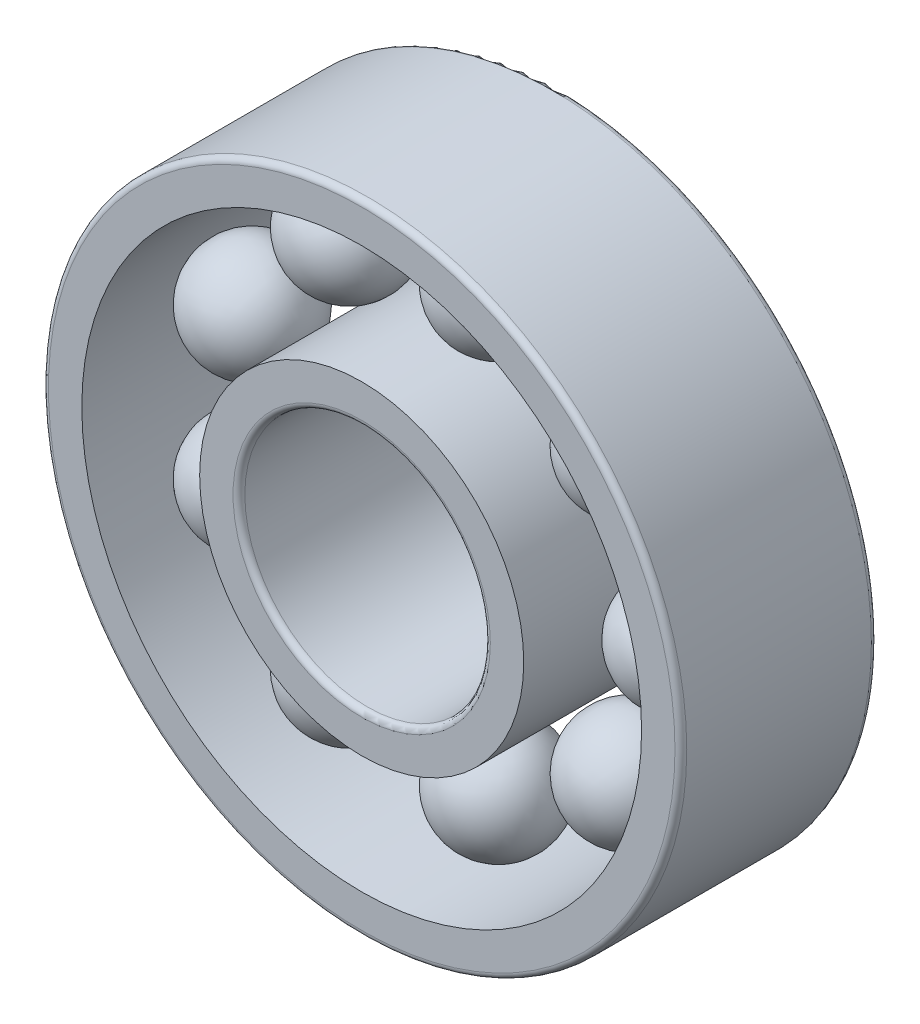
SolidWorks part; units mm, degrees
ref_plane "Front Plane" through (0, 0, 0) normal (0, 0, 1) x (1, 0, 0)
ref_plane "Top Plane" through (0, 0, 0) normal (0, 1, 0) x (1, 0, 0)
ref_plane "Right Plane" through (0, 0, 0) normal (1, 0, 0) x (0, 0, -1)
sketch "S" plane through (0, 0, 0) normal (0, 0, 1) x (1, 0, 0)
  line L0 (-4, 0) -> (4, 0) construction
  circle A0 centre (0, 0) radius 5 construction
  circle A1 centre (0, 0) radius 13 construction
  circle A2 centre (0, 0) radius 6.6 construction
  circle A3 centre (0, 0) radius 11.4 construction
  dimension "ID" = 10
  dimension "OD" = 26
  dimension "IDa" = 13.2
  dimension "ODa" = 22.8
  dimension "B" = 8
ref_axis "Z" through (0, 0, -4.4) along (0, 0, 1)
sketch "InnerS" plane through (0, 0, 0) normal (0, 1, 0) x (1, 0, 0)
  line L0 (5, -4) -> (6.6, -4)
  line L1 (6.6, -4) -> (6.6, 4)
  line L2 (6.6, 4) -> (5, 4)
  line L3 (5, 4) -> (5, -4)
  line L4 (0, -7) -> (0, 7) construction
  dimension "r1" = 5
  dimension "r2" = 6.6
  dimension "z1" = 4
  dimension "z2" = 4
revolve "InnerRing" add sketch "InnerS" angle 360 about L4
sketch "OuterS" plane through (0, 0, 0) normal (0, 1, 0) x (1, 0, 0)
  line L0 (11.4, -4) -> (13, -4)
  line L1 (13, -4) -> (13, 4)
  line L2 (13, 4) -> (11.4, 4)
  line L3 (11.4, 4) -> (11.4, -4)
  line L4 (0, -7) -> (0, 7) construction
  dimension "r1" = 11.4
  dimension "r2" = 13
  dimension "z1" = 4
  dimension "z2" = 4
revolve "OuterRing" add sketch "OuterS" angle 360 about L4
sketch "BallS" plane through (0, 0, 0) normal (0, 1, 0) x (1, 0, 0)
  line L0 (6.72, 0) -> (11.28, 0)
  arc A0 (6.72, 0) -> (11.28, 0) centre (9, 0) ccw
  dimension "r" = 2.28
  dimension "p" = 9
revolve "Ball" add sketch "BallS" angle 360 about L0
pattern_circular "BallsPattern" count 9 over 360 about axis through (0, 0, -4.4) along (0, 0, 1) of bodies 103
fillet "F1" radius 0.24 2 edges at (13, 0, -4) (13, 0, 4)
fillet "F2" radius 0.24 2 edges at (5, 0, -4) (5, 0, 4)
equation "\"r1@InnerS\" = abs(0.5*\"ID@S\")"
equation "\"r2@InnerS\" = abs(0.5*\"IDa@S\")"
equation "\"z1@InnerS\" = abs(-0.5*\"B@S\")"
equation "\"z2@InnerS\" = abs(0.5*\"B@S\")"
equation "\"r1@OuterS\" = abs(0.5*\"ODa@S\")"
equation "\"r2@OuterS\" = abs(0.5*\"OD@S\")"
equation "\"z1@OuterS\" = abs(-0.5*\"B@S\")"
equation "\"z2@OuterS\" = abs(0.5*\"B@S\")"
equation "\"r@BallS\" = abs(0.2375*\"ODa@S\"-0.2375*\"IDa@S\")"
equation "\"p@BallS\" = abs(0.25*\"IDa@S\"+0.25*\"ODa@S\")"
equation "\"N@BallsPattern\" = int(2.417*(0.25*\"IDa@S\"+0.25*\"ODa@S\")/(0.2375*\"ODa@S\"-0.2375*\"IDa@S\"))"
equation "\"r_min@F2\" = \"r_min@F1\""
